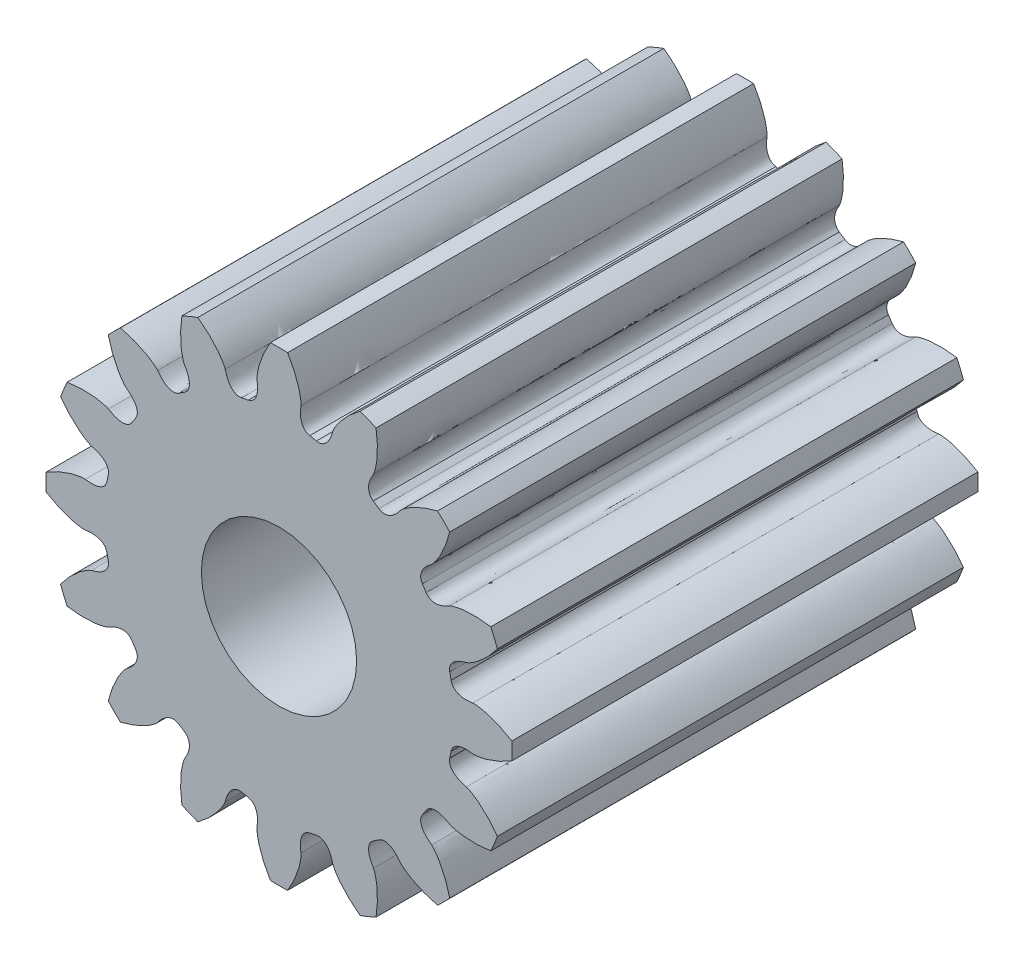
SolidWorks part; units mm, degrees
note: '?' marks a value the reader was unsure of.
ref_plane "정면" through (0, 0, 0) normal (0, 0, 1) x (1, 0, 0)
ref_plane "윗면" through (0, 0, 0) normal (0, 1, 0) x (1, 0, 0)
ref_plane "우측면" through (0, 0, 0) normal (1, 0, 0) x (0, 0, -1)
ref_axis "축1" through (0, 0, -88.99) along (0, 0, 1)?
sketch "스케치1" plane through (0, 0, 0) normal (0, 0, 1) x (1, 0, 0)
  circle A0 centre (0, 0) radius 1.6875
extrude "돌출1" add sketch "스케치1" along normal blind 4.5
sketch "스케치2" plane through (0, 0, 0) normal (0, 0, -1) x (-1, 0, 0)
  arc A0 (-0.0832, 2.2485) -> (0.0832, 2.2485) centre (0, 0)
  arc A1 (-0.297, 1.6612) -> (0.297, 1.6612) centre (0, 0)
  spline S0 degree 3 poles (-0.2125, 1.8705) (-0.2124, 1.8697) (-0.2114, 1.8639) (-0.2137, 1.8934) (-0.2104, 1.91) (-0.2047, 1.9583) (-0.1908, 2.0123) (-0.1674, 2.0825) (-0.1321, 2.1632) (-0.1003, 2.2186) (-0.0832, 2.2485) knots 0 0 0 0 0.005543 0.036908 0.105173 0.210338 0.352403 0.531368 0.747234 1 1 1 1
  spline S1 degree 3 poles (0.2125, 1.8705) (0.2124, 1.8697) (0.2114, 1.8639) (0.2137, 1.8934) (0.2104, 1.91) (0.2047, 1.9583) (0.1908, 2.0123) (0.1674, 2.0825) (0.1321, 2.1632) (0.1003, 2.2186) (0.0832, 2.2485) knots 0 0 0 0 0.005543 0.036908 0.105173 0.210338 0.352403 0.531368 0.747234 1 1 1 1
  spline S2 degree 3 poles (-0.2125, 1.8705) (-0.2108, 1.8589) (-0.2075, 1.8366) (-0.2064, 1.8039) (-0.2084, 1.7733) (-0.2142, 1.7447) (-0.2244, 1.7176) (-0.2407, 1.6926) (-0.2647, 1.6707) (-0.286, 1.6644) (-0.297, 1.6612) knots 0 0 0 0 0.140626 0.270759 0.392102 0.507288 0.620375 0.737138 0.863576 1 1 1 1
  spline S3 degree 3 poles (0.2125, 1.8705) (0.2108, 1.8589) (0.2075, 1.8366) (0.2064, 1.8039) (0.2084, 1.7733) (0.2142, 1.7447) (0.2244, 1.7176) (0.2407, 1.6926) (0.2647, 1.6707) (0.286, 1.6644) (0.297, 1.6612) knots 0 0 0 0 0.140626 0.270759 0.392102 0.507288 0.620375 0.737138 0.863576 1 1 1 1
extrude "돌출2" add sketch "스케치2" against normal blind 4.5
pattern_circular "원형 패턴1" count 16 every 22.5 about axis through (0, 0, -88.99) along (0, 0, 1) of "돌출2"
sketch "스케치3" plane through (0, 0, 4.5) normal (0, 0, 1) x (1, 0, 0)
  circle A0 centre (0, 0) radius 0.75
extrude "컷-돌출1" cut sketch "스케치3" against normal through all
